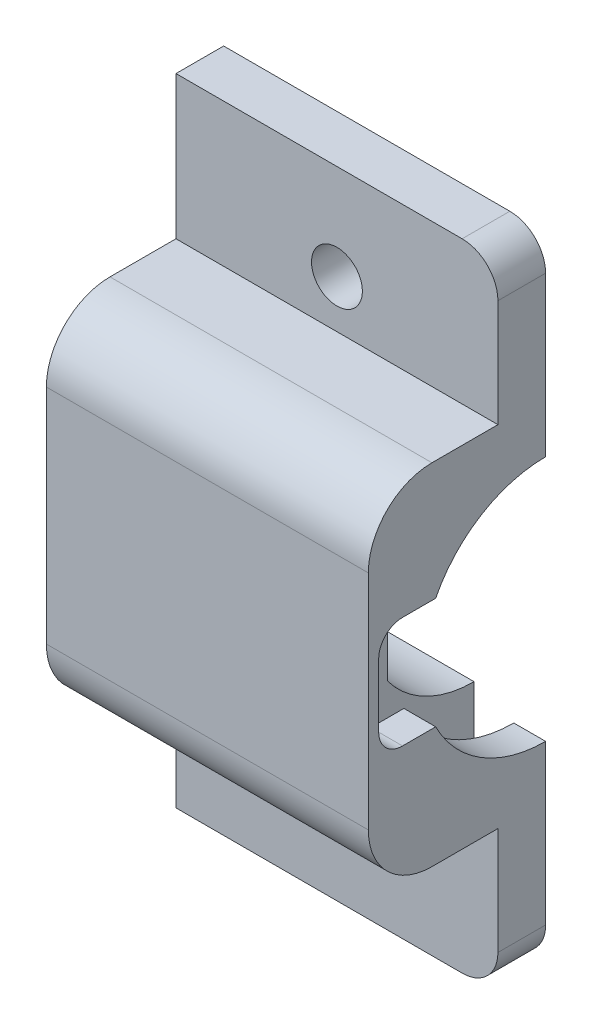
SolidWorks part; units mm, degrees
ref_plane "Front Plane" through (0, 0, 0) normal (0, 0, 1) x (1, 0, 0)
ref_plane "Top Plane" through (0, 0, 0) normal (0, 1, 0) x (1, 0, 0)
ref_plane "Right Plane" through (0, 0, 0) normal (1, 0, 0) x (0, 0, -1)
sketch "Sketch1" plane through (0, 0, 0) normal (0, 0, 1) x (1, 0, 0)
  line L1 (0, 0) -> (20.25, 0)
  line L2 (0, 0) -> (0, 40)
  line L3 (0, 40) -> (20.25, 40)
  line L4 (20.25, 0) -> (20.25, 40)
  dimension "D1" = 40
  dimension "D2" = 20.25
extrude "body" add sketch "Sketch1" along normal blind 3
sketch "Sketch2" plane through (0, 0, 3) normal (0, 0, 1) x (1, 0, 0)
  line L0 (0, 40) -> (0, 0) construction
  line L1 (0, 31) -> (20.25, 31)
  line L2 (0, 31) -> (0, 9)
  line L3 (0, 9) -> (20.25, 9)
  line L4 (20.25, 31) -> (20.25, 9)
  line L5 (20.25, 0) -> (20.25, 40) construction
  point P8 (0, 20)
  point P9 (0, 20)
  dimension "D1" = 22
extrude "hirose" add sketch "Sketch2" along normal blind 8.15
sketch "Sketch3" plane through (0, 0, 0) normal (0, 0, -1) x (-1, 0, 0)
  line L0 (-20.25, 12.25) -> (-20.25, 27.75)
  line L1 (-20.25, 0) -> (-20.25, 40) construction
  line L2 (-20.25, 27.75) -> (-18.25, 27.75)
  line L3 (-18.25, 27.75) -> (-18.25, 12.25)
  line L4 (-20.25, 20) -> (-18.25, 20) construction
  line L5 (-20.25, 12.25) -> (-18.25, 12.25)
  dimension "D1" = 2
  dimension "D2" = 15.5
revolve "hirose-front" cut sketch "Sketch3" angle 360 about L4 region at (19.25, 23.875, 0)
sketch "Sketch4" plane through (0, 0, 0) normal (0, 0, -1) x (-1, 0, 0)
  line L0 (-18.25, 12.25) -> (-18.25, 27.75) construction
  line L1 (-18.25, 30.25) -> (-15.75, 30.25)
  line L2 (-18.25, 30.25) -> (-18.25, 9.75)
  line L3 (-18.25, 9.75) -> (-15.75, 9.75)
  line L4 (-15.75, 30.25) -> (-15.75, 9.75)
  point P4 (-18.25, 20)
  point P5 (-16.25, 20)
  dimension "D1" = 2.5
  dimension "D2" = 20.5
extrude "hirose-mid" cut sketch "Sketch4" against normal offset from surface (10.4 mm away) 0.75 up to face at (10.125, 20, 11.15)
sketch "Sketch5" plane through (20.25, 0, 0) normal (1, 0, 0) x (0, 0, -1)
  line L0 (-7.75, 20) -> (-11.15, 20) construction
  line L1 (-11.15, 9) -> (-11.15, 31) construction
  line L2 (-10.5, 16.5) -> (-10.5, 23.5)
  line L3 (-10.5, 23.5) -> (-6.9147, 23.5)
  line L4 (-10.5, 16.5) -> (-6.9147, 16.5)
  arc A0 (0, 27.75) -> (0, 12.25) centre (0, 20) ccw construction
  arc A1 (-6.9147, 23.5) -> (-6.9147, 16.5) centre (0, 20) ccw
  point P12 (-10.5, 20)
  dimension "D3" = 7.75
  dimension "D1" = 7
  dimension "D2" = 2.75
extrude "Cut-Extrude2" cut sketch "Sketch5" against normal up to surface (2 mm away) up to face at (18.25, 20, 4.7583)
fillet "Fillet1" radius 1.5 2 edges at (19.25, 16.5, 10.5) (19.25, 23.5, 10.5)
sketch "Sketch7" plane through (0, 0, 0) normal (0, 0, -1) x (-1, 0, 0)
  line L0 (-15.75, 20) -> (-1.75, 20) construction
  line L1 (-15.75, 9.75) -> (-15.75, 30.25) construction
  line L2 (-15.75, 13.25) -> (-15.75, 26.75)
  line L3 (-15.75, 26.75) -> (-1.75, 26.75)
  line L4 (-1.75, 26.75) -> (-1.75, 13.25)
  line L5 (-15.75, 13.25) -> (-1.75, 13.25)
  point P8 (-1.75, 20)
  point P9 (-1.75, 20)
  dimension "D1" = 13.5
  dimension "D2" = 14
revolve "Cut-Revolve2" cut sketch "Sketch7" angle 360 about L0 region at (8.75, 23.375, 0)
sketch "Sketch8" plane through (1.75, 0, 0) normal (1, 0, 0) x (0, 0, -1)
  line L0 (-5.45, 23.9825) -> (-5.45, 16.0175)
  arc A0 (0, 26.75) -> (0, 13.25) centre (0, 20) ccw construction
  arc A1 (0, 26.75) -> (0, 13.25) centre (0, 20) ccw construction
  arc A2 (-5.45, 23.9825) -> (-5.45, 16.0175) centre (0, 20) ccw
  point P9 (-6.75, 20)
  dimension "D1" = 6.75
  dimension "D2" = 1.3
extrude "Boss-Extrude3" add sketch "Sketch8" along normal up to surface (14 mm away) up to face at (15.75, 20, 4.5917)
fillet "Fillet2" radius 3 2 edges at (17, 9.75, 10.4) (17, 30.25, 10.4)
fillet "Fillet3" radius 4 2 edges at (10.125, 9, 11.15) (10.125, 31, 11.15)
sketch "Sketch9" plane through (0, 0, 3) normal (0, 0, 1) x (1, 0, 0)
  line L0 (10.125, 40) -> (10.125, 0) construction
  line L1 (20.25, 40) -> (0, 40) construction
  line L2 (0, 0) -> (20.25, 0) construction
  line L3 (0, 27) -> (0, 13) construction
  circle A0 centre (10.125, 34) radius 1.6
  circle A1 centre (10.125, 6) radius 1.6
  point P12 (0, 20)
  dimension "D1" = 3.2
  dimension "D2" = 3.2
  dimension "D3" = 14
  dimension "D4" = 14
extrude "Cut-Extrude3" cut sketch "Sketch9" against normal through all
fillet "Fillet4" radius 2.25 2 edges at (20.25, 0, 1.5) (20.25, 40, 1.5)
